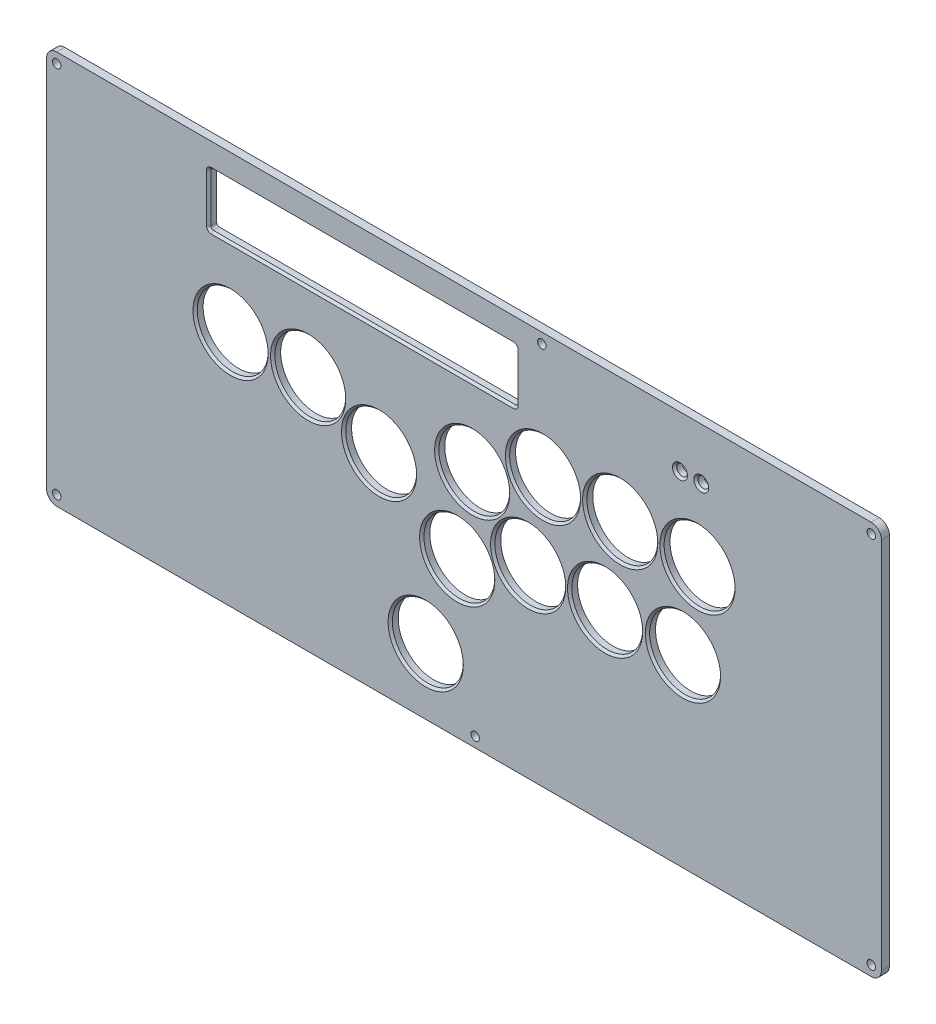
SolidWorks part; units mm, degrees
material "ABS PC"
ref_plane "Front Plane" through (0, 0, 0) normal (0, 0, 1) x (1, 0, 0)
ref_plane "Top Plane" through (0, 0, 0) normal (0, 1, 0) x (1, 0, 0)
ref_plane "Right Plane" through (0, 0, 0) normal (1, 0, 0) x (0, 0, -1)
sketch "草图1" plane through (0, 0, 0) normal (0, 0, 1) x (1, 0, 0)
  line L0 (-95.7877, 63.5) -> (-95.7877, 45.45)
  line L1 (-94.7877, 44.45) -> (18.5123, 44.45)
  line L2 (19.5123, 45.45) -> (19.5123, 63.5)
  line L3 (152.7877, 73.8) -> (-152.7877, 73.8)
  line L4 (-156.5877, -70) -> (-156.5877, 70)
  line L5 (152.7877, -73.8) -> (-152.7877, -73.8)
  line L6 (156.5877, 70) -> (156.5877, -70)
  line L7 (-94.7877, 64.5) -> (18.5123, 64.5)
  arc A0 (-94.7877, 64.5) -> (-95.7877, 63.5) centre (-94.7877, 63.5) ccw
  arc A1 (-95.7877, 45.45) -> (-94.7877, 44.45) centre (-94.7877, 45.45) ccw
  arc A2 (18.5123, 44.45) -> (19.5123, 45.45) centre (18.5123, 45.45) ccw
  arc A3 (19.5123, 63.5) -> (18.5123, 64.5) centre (18.5123, 63.5) ccw
  circle A4 centre (-14.369, -49.1561) radius 13.3
  circle A5 centre (-87.564, 15.4139) radius 13.3
  circle A6 centre (-58.469, 15.2939) radius 13.3
  circle A7 centre (-31.869, 3.9439) radius 13.3
  circle A8 centre (3.071, 15.3539) radius 13.3
  circle A9 centre (24.071, -4.5761) radius 13.3
  circle A10 centre (-2.539, -15.6861) radius 13.3
  circle A11 centre (29.631, 26.8839) radius 13.3
  circle A12 centre (52.921, -4.5761) radius 13.3
  circle A13 centre (58.601, 27.0039) radius 13.3
  circle A14 centre (87.571, 26.7639) radius 13.3
  circle A15 centre (82.131, -4.5761) radius 13.3
  arc A16 (-152.7877, 73.8) -> (-156.5877, 70) centre (-152.7877, 70) ccw
  arc A17 (-156.5877, -70) -> (-152.7877, -73.8) centre (-152.7877, -70) ccw
  arc A18 (152.7877, -73.8) -> (156.5877, -70) centre (152.7877, -70) ccw
  arc A19 (156.5877, 70) -> (152.7877, 73.8) centre (152.7877, 70) ccw
  circle A20 centre (81.0162, 54.475) radius 2
  circle A21 centre (89.0162, 54.475) radius 2
  circle A22 centre (152.7877, -70) radius 1.6
  circle A23 centre (152.7877, 70) radius 1.6
  circle A24 centre (4.2122, -70) radius 1.6
  circle A25 centre (29.2122, 70) radius 1.6
  circle A26 centre (-152.7877, 70) radius 1.6
  circle A27 centre (-152.7877, -70) radius 1.6
  point P60 (0, 0)
extrude "凸台-拉伸1" add sketch "草图1" along normal blind 3 contours L3 A16 L4 A17 L5 A18 L6 A19
extrude "切除-拉伸1" cut sketch "草图1<3>" against normal through all and the other way through all from surface contours L1 A2 L2 A3 L7 A0 L0 A1 | A4 | A5 | A12 | A13 | A11 | A9 | A8 | A10 | A7 | A6 | A15 | A14 | A22 | A24 | A27 | A23 | A25 | A26 | A21 | A20 starting at face at (0, 0, 3)
sketch "草图1<3>" plane through (0, 0, 0) normal (0, 0, 1) x (1, 0, 0) same geometry as "草图1"
chamfer "倒角1" distance 0.8 36 edges at (156.5877, 0, 3) (155.4747, -72.687, 3) (0, -73.8, 3) (-155.4747, -72.687, 3) (-156.5877, 0, 3) (-155.4747, 72.687, 3) (0, 73.8, 3) (155.4747, 72.687, 3) (-95.7877, 54.475, 3) (-95.4948, 44.7429, 3) (-38.1377, 44.45, 3) (19.2194, 44.7429, 3) (19.5123, 54.475, 3) (19.2194, 64.2071, 3) (-38.1377, 64.5, 3) (-95.4948, 64.2071, 3) (83.0162, 54.475, 3) (91.0162, 54.475, 3) (-151.1877, 70, 3) (30.8122, 70, 3) (42.931, 26.8839, 3) (37.371, -4.5761, 3) (16.371, 15.3539, 3) (10.761, -15.6861, 3) (71.901, 27.0039, 3) (66.221, -4.5761, 3) (-74.264, 15.4139, 3) (-1.069, -49.1561, 3) (154.3877, -70, 3) (5.8122, -70, 3) (-151.1877, -70, 3) (154.3877, 70, 3) (100.871, 26.7639, 3) (95.431, -4.5761, 3) (-18.569, 3.9439, 3) (-45.169, 15.2939, 3)
other "删除面1" face at (-150.3877, 70, 3) and patch yes
other "删除面2" face at (31.6122, 70, 3) and patch yes
other "删除面3" face at (155.1877, 70, 3) and patch yes
other "删除面4" face at (-150.3877, -70, 3) and patch yes
other "删除面5" face at (6.6122, -70, 3) and patch yes
other "删除面6" face at (155.1877, -70, 3) and patch yes
other "删除面7" face at (-156.1877, 0, 2.6) face at (-154.8398, -72.0521, 2.6) face at (0, -73.4, 2.6) face at (-154.8398, 72.0521, 2.6) face at (0, 73.4, 2.6) face at (154.8398, 72.0521, 2.6) face at (156.1877, 0, 2.6) face at (154.8398, -72.0521, 2.6) and patch yes
